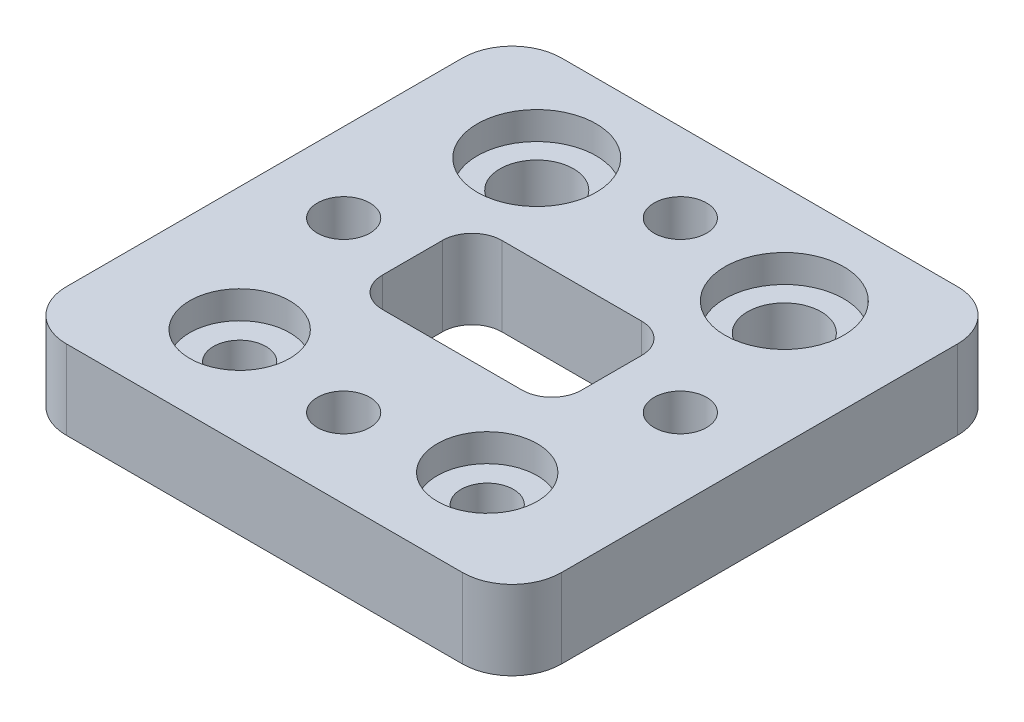
SolidWorks part; units mm, degrees
other "Marca1"
sketch "Croquis2" plane through (25, 8, 25) normal (0.0944, 0.803, 0.5885) x (0.9369, -0.2715, 0.2201)
ref_plane "Alzado" through (0, 0, 0) normal (0, 0, 1) x (1, 0, 0)
ref_plane "Planta" through (0, 0, 0) normal (0, 1, 0) x (1, 0, 0)
ref_plane "Vista lateral" through (0, 0, 0) normal (1, 0, 0) x (0, 0, -1)
sketch "Croquis1" plane through (0, 0, 0) normal (0, 1, 0) x (1, 0, 0)
  line L0 (-20, -25) -> (20, -25)
  line L2 (-25, -20) -> (-25, 20)
  line L4 (25, -20) -> (25, 20)
  line L5 (-12.5, 15) -> (-12.5, -15) construction
  line L8 (-7.0602, -6.0357) -> (7.0602, -6.0357)
  line L9 (-20, 25) -> (20, 25)
  line L10 (-10.0602, -3.0357) -> (-10.0602, 3.0357)
  line L11 (-7.0602, 6.0357) -> (7.0602, 6.0357)
  line L12 (10.0602, -3.0357) -> (10.0602, 3.0357)
  line L13 (-12.5, 15) -> (12.5, 15) construction
  line L14 (0, 0) -> (0, -17) construction
  line L15 (0, 0) -> (17, 0) construction
  circle A0 centre (-12.5, -15) radius 5.05
  circle A1 centre (-12.5, -15) radius 2.65
  circle A2 centre (-12.5, 15) radius 6
  circle A3 centre (-12.5, 15) radius 3.72
  arc A10 (-7.0602, -6.0357) -> (-10.0602, -3.0357) centre (-7.0602, -3.0357) cw
  arc A11 (7.0602, -6.0357) -> (10.0602, -3.0357) centre (7.0602, -3.0357) ccw
  arc A12 (10.0602, 3.0357) -> (7.0602, 6.0357) centre (7.0602, 3.0357) ccw
  arc A13 (-10.0602, 3.0357) -> (-7.0602, 6.0357) centre (-7.0602, 3.0357) cw
  arc A14 (-20, -25) -> (-25, -20) centre (-20, -20) cw
  arc A15 (25, -20) -> (20, -25) centre (20, -20) cw
  arc A16 (25, 20) -> (20, 25) centre (20, 20) ccw
  arc A17 (-25, 20) -> (-20, 25) centre (-20, 20) cw
  circle A19 centre (0, -17) radius 2.65
  circle A20 centre (-17, 0) radius 2.65
  circle A21 centre (0, 17) radius 2.65
  circle A22 centre (17, 0) radius 2.65
  circle A23 centre (12.5, -15) radius 2.65
  circle A24 centre (12.5, -15) radius 5.05
  circle A25 centre (12.5, 15) radius 3.72
  circle A26 centre (12.5, 15) radius 6
  point P0 (0, 0)
  point P1 (0, 15)
  point P2 (0, 0)
  point P3 (-12.5, 0)
  point P7 (0, 0)
  point P47 (0, -6.0357)
  point P50 (0, 6.0357)
  point P54 (10.0602, 0)
  point P55 (-10.0602, 0)
  point P56 (25, 0)
  point P57 (-25, 0)
  point P59 (0, 25)
  point P61 (0, 0)
  dimension "D1" = 10.1
  dimension "D2" = 5.3
  dimension "D3" = 12
  dimension "D4" = 7.44
  dimension "D5" = 4
  dimension "D6" = 3
  dimension "D7" = 5
  dimension "D9" = 25
  dimension "D10" = 17
  dimension "D11" = 5.3
  dimension "D15" = 5
  dimension "D17" = 14.1204
  dimension "D18" = 6.0713
  dimension "D12" = 30
  dimension "D14" = 40
  dimension "D16" = 40
  dimension "D19" = 17
extrude "Saliente-Extruir2" add sketch "Croquis1" along normal blind 8 contours L9 L2 L0 L4 A26 A0 A2 A20 L10 A13 L11 A12 L12 A11 L8 A10 | A0 A1 | A2 A3 | A26 A25 | A24 A23 region at (-23.0355, 0, 23.0355) region at (-17.4072, 0, 15) region at (-18.3303, 0, -15) region at (7.5928, 0, 15) region at (6.6697, 0, -15)
extrude "Cortar-Extruir1" cut sketch "Croquis1<4>" against normal blind 2.8 from surface contours A0 A1 | A2 A3 | A26 A25 | A24 A23 region at (-17.4072, 0, 15) region at (-18.3303, 0, -15) region at (7.5928, 0, 15) region at (6.6697, 0, -15) starting at face at (17, 8, 2.65)
sketch "Croquis1<4>" plane through (0, 0, 0) normal (0, 1, 0) x (1, 0, 0) same geometry as "Croquis1"
